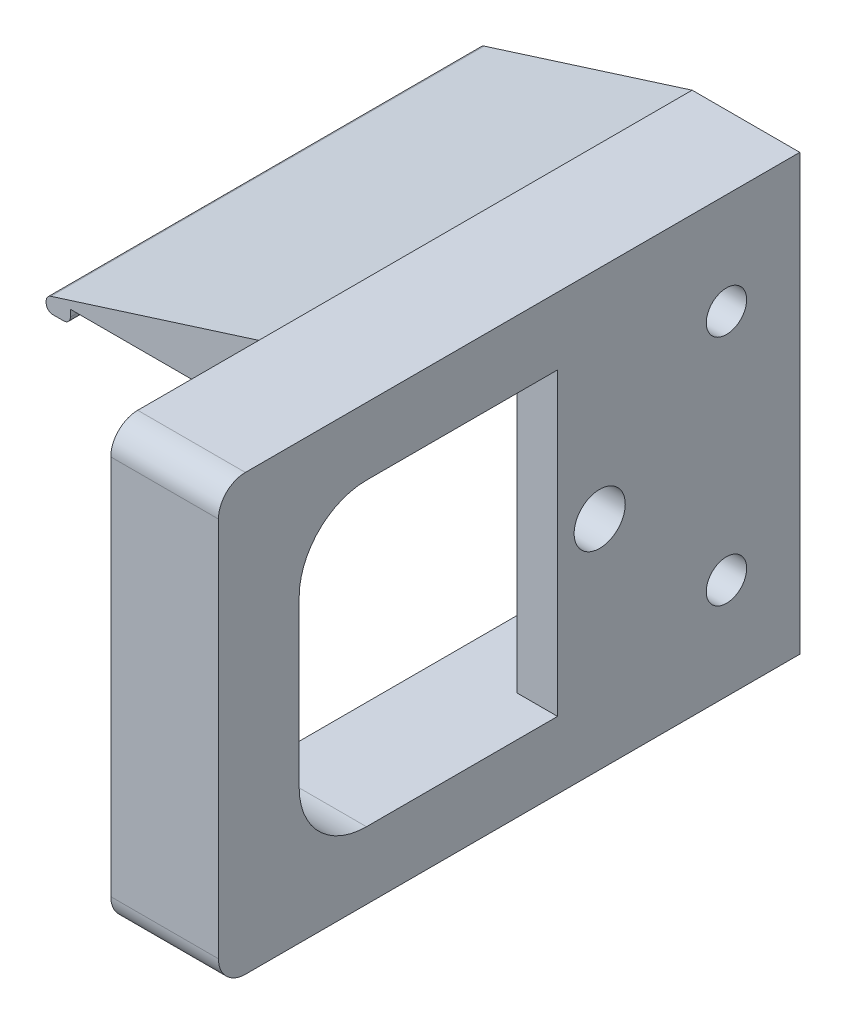
SolidWorks part; units mm, degrees
ref_plane "Front Plane" through (0, 0, 0) normal (0, 0, 1) x (1, 0, 0)
ref_plane "Top Plane" through (0, 0, 0) normal (0, 1, 0) x (1, 0, 0)
ref_plane "Right Plane" through (0, 0, 0) normal (1, 0, 0) x (0, 0, -1)
sketch "U" plane through (0, 0, 0) normal (1, 0, 0) x (0, 0, -1)
  line L0 (0, 22.3) -> (0, 27.3)
  line L1 (0, 0) -> (-32.2, 0)
  line L3 (0, 22.3) -> (-32.2, 22.3)
  line L4 (-37.2, 5) -> (-37.2, 17.3)
  line L5 (0, 27.3) -> (-41.2, 27.3)
  line L6 (-43.2, 25.3) -> (-43.2, -3)
  line L7 (-41.2, -5) -> (0, -5)
  line L8 (0, -5) -> (0, 0)
  arc A0 (-41.2, -5) -> (-43.2, -3) centre (-41.2, -3) cw
  arc A1 (-41.2, 27.3) -> (-43.2, 25.3) centre (-41.2, 25.3) ccw
  arc A2 (-37.2, 5) -> (-32.2, 0) centre (-32.2, 5) ccw
  arc A3 (-37.2, 17.3) -> (-32.2, 22.3) centre (-32.2, 17.3) cw
  point P15 (-37.2, 0)
  point P18 (-37.2, 22.3)
  dimension "D5" = 2
  dimension "D6" = 5
  dimension "D1" = 37.2
  dimension "D2" = 22.3
  dimension "D3" = 5
  dimension "D4" = 6
extrude "Boss-Extrude1" add sketch "U" against normal blind 5 and the other way blind 3
ref_plane "Plano1" through (0, 11.15, 0) normal (0, 1, 0) x (1, 0, 0)
sketch "Sketch2" plane through (0, 0, 0) normal (1, 0, 0) x (0, 0, -1)
  line L0 (0, 27.3) -> (-41.2, 27.3) construction
  line L1 (0, -5) -> (-18, -5)
  line L2 (0, -5) -> (0, 27.3)
  line L3 (0, 27.3) -> (-18, 27.3)
  line L4 (-18, -5) -> (-18, 27.3)
  circle A0 centre (-14.87, 11.15) radius 1.9
  dimension "D2" = 14.87
  dimension "D3" = 3.8
  dimension "D1" = 18
extrude "Boss-Extrude2" add sketch "Sketch2" along normal blind 3
sketch "AgujerosMotor" plane through (3, 0, 0) normal (1, 0, 0) x (0, 0, -1)
  line L0 (-5.45, 22.3) -> (-5.45, 0) construction
  line L1 (-18, 22.3) -> (0, 22.3) construction
  line L2 (-18, 22.3) -> (-18, 0) construction
  line L3 (-18, 0) -> (0, 0) construction
  line L4 (0, 22.3) -> (0, 0) construction
  line L5 (-5.45, 11.15) -> (0, 11.15) construction
  circle A0 centre (-5.45, 2.5) radius 1.5
  circle A1 centre (-5.45, 19.8) radius 1.5
  dimension "D2" = 3
  dimension "D1" = 5.45
  dimension "D3" = 2.5
extrude "Cut-Extrude1" cut sketch "AgujerosMotor" against normal up to next
sketch "Sketch5" plane through (-5, 0, 0) normal (-1, 0, 0) x (0, 0, 1)
  line L0 (32.2, 22.3) -> (0, 22.3) construction
  line L5 (0, 27.3) -> (32.2, 27.3)
  line L6 (0, 27.3) -> (0, 22.3)
  line L7 (0, 22.3) -> (32.2, 22.3)
  line L8 (32.2, 27.3) -> (32.2, 22.3)
  arc A0 (37.2, 17.3) -> (32.2, 22.3) centre (32.2, 17.3) ccw construction
extrude "Boss-Extrude3" add sketch "Sketch5" along normal blind 15.8
chamfer "Chaflán1" distance 15.8 distance2 5 1 edges at (-20.8, 27.3, 16.1) first distance on face at (-7.6, 27.3, 24.4667)
sketch "Croquis1" plane through (0, 22.3, 0) normal (0, -1, 0) x (1, 0, 0)
  line L0 (-20.8, 32.2) -> (-5, 32.2) construction
  line L1 (-20.8, 0) -> (-19, 0)
  line L2 (-20.8, 0) -> (-20.8, 32.2)
  line L3 (-20.8, 32.2) -> (-19, 32.2)
  line L4 (-19, 0) -> (-19, 32.2)
  dimension "D1" = 1.8
extrude "Saliente-Extruir1" add sketch "Croquis1" along normal blind 1
fillet "Redondeo2" radius 0.5 3 edges at (-20.8, 22.3, 16.1) (-20.8, 21.3, 16.1) (-19, 21.3, 16.1)
